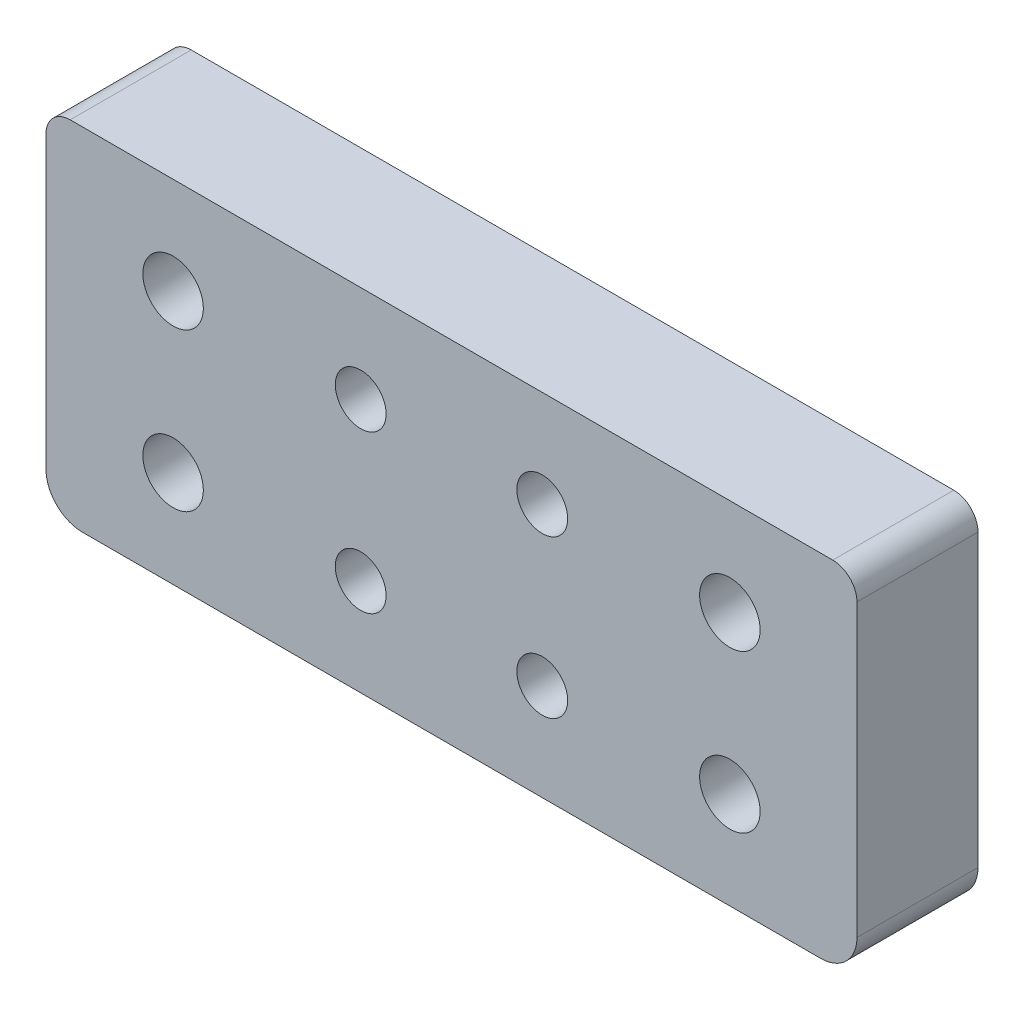
SolidWorks part; units mm, degrees
ref_plane "前视基准面" through (0, 0, 0) normal (0, 0, 1) x (1, 0, 0)
ref_plane "上视基准面" through (0, 0, 0) normal (0, 1, 0) x (1, 0, 0)
ref_plane "右视基准面" through (0, 0, 0) normal (1, 0, 0) x (0, 0, -1)
sketch "草图1" plane through (0, 0, 0) normal (0, 0, 1) x (1, 0, 0)
  line L0 (-48.8239, 0) -> (56.5192, 0) construction
  line L1 (-33.5, -8) -> (33.5, -8)
  line L2 (-33.5, -8) -> (-33.5, 8)
  line L3 (-33.5, 8) -> (33.5, 8)
  line L4 (33.5, -8) -> (33.5, 8)
  line L5 (-33.5, -8) -> (33.5, 8) construction
  line L6 (-33.5, 8) -> (33.5, -8) construction
  line L7 (0, 28.7883) -> (0, -27.5036) construction
  point P0 (0, 0)
  dimension "D1" = 16
  dimension "D2" = 67
extrude "凸台-拉伸1" add sketch "草图1" along normal blind 10
hole_wizard "M5 螺纹孔1" positions "草图3" profile "草图4" tap size "M5" standard "GB"
sketch "草图3" plane through (0, 0, 10) normal (0, 0, 1) x (1, 0, 0)
  line L0 (0, 0) -> (0, 19.7721) construction
  point P0 (-7.5, 0)
  point P2 (7.5, 0)
  dimension "D1" = 15
sketch "草图4" plane through (-7.5, 0, 10) normal (1, 0, 0) x (0, -1, 0)
  line L0 (0, 0) -> (0, 13.6618)
  line L1 (0, 13.6618) -> (2.1, 12.4)
  line L2 (2.1, 12.4) -> (2.1, 0)
  line L5 (2.1, 0) -> (0, 0)
  line L10 (0, 13.6618) -> (-2.1, 12.4) construction
  line L11 (0, -6.35) -> (0, 107.95) construction
  dimension "螺纹孔钻头直径" = 4.2
  dimension "螺纹孔钻头深度" = 12.4
  dimension "导头角度" = 118
cosmetic thread "孔螺蚊线1" parameters "D1"=10, "D2"=5
cosmetic thread "孔螺蚊线2" parameters "D1"=10, "D2"=5
hole_wizard "M6 螺纹孔1" positions "草图6" profile "草图7" tap size "M6" standard "GB"
sketch "草图6" plane through (0, 0, 10) normal (0, 0, 1) x (1, 0, 0)
  line L0 (0, 0) -> (0, 15.7522) construction
  point P0 (-23, 0)
  point P10 (23, 0)
  dimension "D1" = 46
sketch "草图7" plane through (-23, 0, 10) normal (1, 0, 0) x (0, -1, 0)
  line L0 (0, 0) -> (0, 16.5022)
  line L1 (0, 16.5022) -> (2.5, 15)
  line L2 (2.5, 15) -> (2.5, 0)
  line L5 (2.5, 0) -> (0, 0)
  line L10 (0, 16.5022) -> (-2.5, 15) construction
  line L11 (0, -6.35) -> (0, 107.95) construction
  dimension "螺纹孔钻头直径" = 5
  dimension "螺纹孔钻头深度" = 15
  dimension "导头角度" = 118
cosmetic thread "孔螺蚊线3" parameters "D1"=12, "D2"=6
cosmetic thread "孔螺蚊线4" parameters "D1"=12, "D2"=6
fillet "圆角1" radius 2 4 edges at (-33.5, -8, 5) (-33.5, 8, 5) (33.5, 8, 5) (33.5, -8, 5)
sketch "草图8" plane through (0, -8, 0) normal (0, -1, 0) x (1, 0, 0)
  line L1 (-33.5, 10) -> (33.5, 10)
  line L2 (-33.5, 10) -> (-33.5, 0)
  line L3 (-33.5, 0) -> (33.5, 0)
  line L4 (33.5, 10) -> (33.5, 0)
extrude "凸台-拉伸2" add sketch "草图8" along normal blind 13
other "删除面1" face at (-32.7071, -7.2071, 5) face at (-32.5, -8, 5) and patch yes
other "删除面2" face at (32.7071, -7.2071, 5) face at (32.5, -8, 5) and patch yes
ref_plane "基准面1" through (0, -6.5, 0) normal (0, -1, 0) x (-1, 0, 0)
mirror "镜向1" about plane through (0, -6.5, 0) normal (0, -1, 0) of "M5 螺纹孔1", "M6 螺纹孔1"
cosmetic thread "孔螺纹线1" parameters "D1"=12, "D2"=6
cosmetic thread "孔螺纹线2" parameters "D1"=12, "D2"=6
cosmetic thread "孔螺纹线3" parameters "D1"=10, "D2"=5
cosmetic thread "孔螺纹线4" parameters "D1"=10, "D2"=5
fillet "圆角2" radius 3 2 edges at (33.5, -21, 5) (-33.5, -21, 5)
